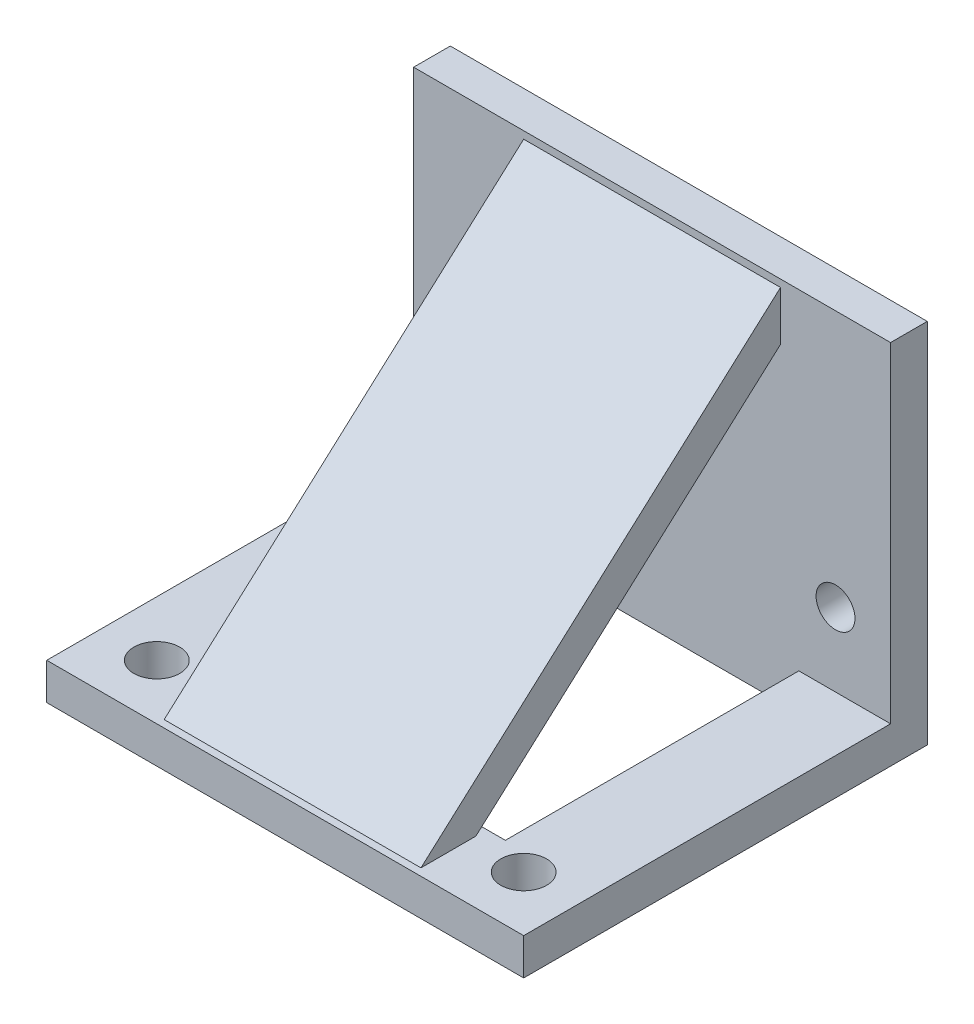
SolidWorks part; units mm, degrees
other "Markup1"
sketch "Sketch16" [suppressed] plane through (60, 62, 45) normal (0.9182, 0.3955, 0.0203) x (-0.0959, 0.2718, -0.9576)
ref_plane "Front" through (0, 0, 0) normal (0, 0, 1) x (1, 0, 0)
ref_plane "Top" through (0, 0, 0) normal (0, 1, 0) x (1, 0, 0)
ref_plane "Right" through (0, 0, 0) normal (1, 0, 0) x (0, 0, -1)
sketch "Sketch1" plane through (0, 0, 0) normal (0, 0, 1) x (1, 0, 0)
  line L1 (-32.5, 0) -> (32.5, 0)
  line L2 (-32.5, 0) -> (-32.5, 50)
  line L3 (-32.5, 50) -> (32.5, 50)
  line L4 (32.5, 0) -> (32.5, 50)
  line L7 (0, 11.4259) -> (0, -9.2664) construction
  point P4 (0, 0)
  dimension "D1" = 50
  dimension "D2" = 65
extrude "Boss-Extrude1" add sketch "Sketch1" along normal blind 5 contours L1 L4 L3 L2 region at (0, 25, 0)
sketch "Sketch2" plane through (0, 0, 0) normal (0, 1, 0) x (1, 0, 0)
  line L0 (0, 7.4706) -> (0, -16.6901) construction
  line L1 (-25, 85) -> (-25, 5) construction
  line L2 (-32.5, 0) -> (-17.5, 0)
  line L3 (-32.5, 0) -> (-32.5, 91)
  line L4 (-32.5, 91) -> (-17.5, 91)
  line L5 (-17.5, 0) -> (-17.5, 91)
  line L8 (17.5, 0) -> (17.5, 91)
  line L9 (32.5, 91) -> (17.5, 91)
  line L10 (32.5, 0) -> (32.5, 91)
  line L11 (32.5, 0) -> (17.5, 0)
  line L12 (-21.75, 85) -> (-21.75, 5)
  line L15 (-28.25, 85) -> (-28.25, 5)
  line L16 (25, 85) -> (25, 5) construction
  line L17 (21.75, 85) -> (21.75, 5)
  line L18 (28.25, 85) -> (28.25, 5)
  arc A4 (-21.75, 85) -> (-28.25, 85) centre (-25, 85) ccw
  arc A5 (-28.25, 5) -> (-21.75, 5) centre (-25, 5) ccw
  arc A6 (21.75, 85) -> (28.25, 85) centre (25, 85) cw
  arc A7 (28.25, 5) -> (21.75, 5) centre (25, 5) cw
  point P9 (-25, 45)
  point P17 (25, 45)
  dimension "D3" = 3.25
  dimension "D5" = 5
  dimension "D1" = 91
  dimension "D2" = 15
  dimension "D4" = 6
extrude "Boss-Extrude3" [suppressed] add sketch "Sketch2" along normal blind 5
sketch "Sketch7" plane through (0, 0, 5) normal (0, 0, 1) x (1, 0, 0)
  line L1 (-32.5, 50) -> (32.5, 50)
  line L2 (-32.5, 50) -> (-32.5, 0)
  line L3 (-32.5, 0) -> (32.5, 0)
  line L4 (32.5, 50) -> (32.5, 0)
extrude "Boss-Extrude5" add sketch "Sketch7" along normal blind 50
sketch "Sketch8" plane through (-32.5, 0, 0) normal (-1, 0, 0) x (0, 0, 1)
  line L0 (55, 50) -> (5, 50)
  line L1 (55, 50) -> (0, 50) construction
  line L2 (5, 50) -> (5, 49)
  line L3 (5, 49) -> (54, 5)
  line L5 (54, 5) -> (55, 5)
  line L6 (55, 50) -> (55, 0) construction
  line L7 (55, 5) -> (55, 50)
  line L8 (0, 0) -> (0, 50) construction
  dimension "D1" = 5
  dimension "D2" = 1
  dimension "D3" = 1
  dimension "D4" = 5
extrude "Cut-Extrude4" cut sketch "Sketch8" against normal through all
sketch "Sketch9" plane through (0, 0, 5) normal (0, 0, 1) x (1, 0, 0)
  line L0 (19, 56.4751) -> (19, -5.9092) construction
  line L1 (32.5, 50) -> (-32.5, 50) construction
  line L2 (0, 50) -> (0, 0) construction
  line L3 (-19, 58.7509) -> (-19, -17.8238) construction
  line L4 (-32.5, 0) -> (32.5, 0) construction
  circle A0 centre (-25, 15) radius 2.65
  circle A3 centre (25, 15) radius 2.65
  dimension "D1" = 5.3
  dimension "D2" = 25
  dimension "D3" = 15
  dimension "D4" = 19
  dimension "D5" = 19
extrude "Cut-Extrude5" cut sketch "Sketch9" against normal through all
sketch "Sketch10" plane through (0, 5, 0) normal (0, 1, 0) x (1, 0, 0)
  line L0 (0, 0) -> (0, -55) construction
  line L1 (32.5, -55) -> (-32.5, -55) construction
  circle A0 centre (-25, -47.5) radius 3.125
  circle A2 centre (25, -47.5) radius 3.125
  dimension "D1" = 6.25
  dimension "D2" = 7.5
  dimension "D3" = 25
extrude "Cut-Extrude6" cut sketch "Sketch10" against normal through all
sketch "Sketch11" [suppressed] plane through (0, 0, 10) normal (0, 0, 1) x (1, 0, 0)
  line L0 (-32.5, 0) -> (32.5, 0) construction
  line L1 (-32.5, 50) -> (-17.5, 50)
  line L2 (-32.5, 50) -> (-32.5, 0)
  line L3 (-32.5, 0) -> (-17.5, 0)
  line L4 (-17.5, 50) -> (-17.5, 0)
  line L6 (0, 50) -> (0, 0) construction
  line L7 (-32.5, 50) -> (32.5, 50) construction
  line L8 (17.5, 50) -> (17.5, 0)
  line L9 (32.5, 0) -> (17.5, 0)
  line L10 (32.5, 50) -> (32.5, 0)
  line L11 (32.5, 50) -> (17.5, 50)
  dimension "D1" = 15
extrude "Boss-Extrude6" [suppressed] add sketch "Sketch11" along normal blind 35
sketch "Sketch12" [suppressed] plane through (-32.5, 0, 0) normal (-1, 0, 0) x (0, 0, 1)
  line L0 (10, 50) -> (10, 35)
  line L1 (45, 50) -> (0, 50) construction
  line L2 (10, 35) -> (35, 5)
  line L3 (35, 5) -> (45, 5)
  line L4 (45, 50) -> (45, 0) construction
  line L5 (45, 5) -> (45, 50)
  line L6 (45, 50) -> (10, 50)
  line L7 (45, 0) -> (-122, 0) construction
  line L8 (0, 5) -> (0, 50) construction
  dimension "D1" = 15
  dimension "D2" = 5
  dimension "D3" = 10
  dimension "D4" = 10
extrude "Cut-Extrude7" [suppressed] cut sketch "Sketch12" against normal through all
sketch "Sketch20" [suppressed] plane through (0, 0, 10) normal (0, 0, 1) x (1, 0, 0)
  line L0 (32.5, 50) -> (32.5, 0) construction
  line L5 (-32.5, 50) -> (32.5, 50)
  line L6 (-32.5, 50) -> (-32.5, 55)
  line L7 (-32.5, 55) -> (32.5, 55)
  line L8 (32.5, 50) -> (32.5, 55)
  dimension "D1" = 5
extrude "Boss-Extrude7" [suppressed] add sketch "Sketch20" against normal up to surface (10 mm away)
sketch "Sketch13" [suppressed] plane through (0, 0, 5) normal (0, 0, 1) x (1, 0, 0)
  line L0 (0, 62) -> (0, 0) construction
  line L1 (32.5, 55) -> (-32.5, 55) construction
  circle A0 centre (-25, 20) radius 3.125
  circle A1 centre (25, 20) radius 3.125
  dimension "D1" = 6.25
  dimension "D2" = 35
  dimension "D3" = 25
extrude "Cut-Extrude8" [suppressed] cut sketch "Sketch13" against normal blind 15
sketch "Sketch14" [suppressed] plane through (0, 5, 0) normal (0, 1, 0) x (1, 0, 0)
  line L1 (-17.5, -45) -> (-32.5, -45) construction
  line L2 (-17.5, -45) -> (-32.5, -45)
  line L3 (-32.5, -35) -> (-32.5, -45) construction
  line L4 (-32.5, -35) -> (-32.5, -45)
  line L5 (0, 0) -> (0, -45) construction
  circle A0 centre (-25, -40) radius 3.125
  circle A1 centre (25, -40) radius 3.125
  point P2 (-25, -45)
  point P6 (-32.5, -40)
  dimension "D1" = 6.25
extrude "Cut-Extrude9" [suppressed] cut sketch "Sketch14" against normal blind 15 contours A0 | A1
sketch "Sketch21" [suppressed] plane through (0, 0, 0) normal (0, 1, 0) x (1, 0, 0)
  line L0 (0, 10.9853) -> (0, -16.7679) construction
  line L1 (32.5, -5) -> (-32.5, -5) construction
  line L2 (32.5, 3) -> (47.5, 3)
  line L3 (32.5, 3) -> (32.5, -5)
  line L4 (32.5, -5) -> (47.5, -5)
  line L5 (47.5, 3) -> (47.5, -5)
  line L6 (34.1921, -1) -> (44.0025, -1) construction
  line L7 (32.5, 3) -> (47.5, 3)
  line L8 (32.5, -5) -> (47.5, -5)
  line L9 (32.5, 3) -> (47.5, 3)
  line L10 (32.5, -5) -> (47.5, -5)
  line L11 (32.5, 3) -> (47.5, 3)
  line L12 (32.5, -5) -> (47.5, -5)
  line L13 (32.5, 3) -> (47.5, 3)
  line L14 (32.5, -5) -> (47.5, -5)
  line L15 (32.5, 3) -> (47.5, 3)
  line L16 (32.5, -5) -> (47.5, -5)
  line L17 (32.5, 3) -> (47.5, 3)
  line L18 (32.5, -5) -> (47.5, -5)
  line L19 (32.5, 3) -> (47.5, 3)
  line L20 (32.5, -5) -> (47.5, -5)
  line L21 (32.5, 3) -> (47.5, 3)
  line L22 (32.5, -5) -> (47.5, -5)
  line L23 (32.5, 3) -> (47.5, 3)
  line L24 (32.5, -5) -> (47.5, -5)
  line L29 (32.5, 0) -> (32.5, 91) construction
  line L30 (32.5, 3) -> (47.5, 3)
  line L31 (32.5, -5) -> (47.5, -5)
  line L32 (32.5, 3) -> (47.5, 3)
  line L33 (32.5, -5) -> (47.5, -5)
  line L34 (32.5, 3) -> (47.5, 3)
  line L35 (32.5, -5) -> (47.5, -5)
  line L36 (32.5, 3) -> (47.5, 3)
  line L37 (32.5, -5) -> (47.5, -5)
  line L38 (32.5, 3) -> (47.5, 3)
  line L39 (32.5, -5) -> (47.5, -5)
  line L40 (32.5, 3) -> (47.5, 3)
  line L41 (32.5, -5) -> (47.5, -5)
  line L42 (32.5, 3) -> (47.5, 3)
  line L43 (32.5, -5) -> (47.5, -5)
  line L44 (32.5, 3) -> (47.5, 3)
  line L45 (32.5, -5) -> (47.5, -5)
  line L46 (32.5, 3) -> (47.5, 3)
  line L47 (32.5, -5) -> (47.5, -5)
  line L48 (32.5, 3) -> (47.5, 3)
  line L49 (32.5, -5) -> (47.5, -5)
  line L50 (-47.5, 3) -> (-32.5, 3)
  line L51 (-47.5, 3) -> (-47.5, -5)
  line L52 (-47.5, -5) -> (-32.5, -5)
  line L53 (-32.5, 3) -> (-32.5, -5)
  line L54 (-47.5, -1) -> (-32.5, -1) construction
  line L55 (-47.5, 3) -> (-32.5, 3)
  line L56 (-47.5, -5) -> (-32.5, -5)
  line L57 (-47.5, 3) -> (-32.5, 3)
  line L58 (-47.5, -5) -> (-32.5, -5)
  line L59 (-47.5, 3) -> (-32.5, 3)
  line L60 (-47.5, -5) -> (-32.5, -5)
  line L61 (-47.5, 3) -> (-32.5, 3)
  line L62 (-47.5, -5) -> (-32.5, -5)
  line L63 (-47.5, 3) -> (-32.5, 3)
  line L64 (-47.5, -5) -> (-32.5, -5)
  line L65 (-47.5, 3) -> (-32.5, 3)
  line L66 (-47.5, -5) -> (-32.5, -5)
  line L67 (-47.5, 3) -> (-32.5, 3)
  line L68 (-47.5, -5) -> (-32.5, -5)
  line L69 (-47.5, 3) -> (-32.5, 3)
  line L70 (-47.5, -5) -> (-32.5, -5)
  line L71 (-47.5, 3) -> (-32.5, 3)
  line L72 (-47.5, -5) -> (-32.5, -5)
  line L73 (-47.5, 3) -> (-32.5, 3)
  line L74 (-47.5, -5) -> (-32.5, -5)
  line L75 (-47.5, 3) -> (-32.5, 3)
  line L76 (-47.5, -5) -> (-32.5, -5)
  line L77 (-47.5, 3) -> (-32.5, 3)
  line L78 (-47.5, -5) -> (-32.5, -5)
  line L79 (-47.5, 3) -> (-32.5, 3)
  line L80 (-47.5, -5) -> (-32.5, -5)
  line L81 (-47.5, 3) -> (-32.5, 3)
  line L82 (-47.5, -5) -> (-32.5, -5)
  line L83 (-47.5, 3) -> (-32.5, 3)
  line L84 (-47.5, -5) -> (-32.5, -5)
  line L85 (-47.5, 3) -> (-32.5, 3)
  line L86 (-47.5, -5) -> (-32.5, -5)
  line L87 (-47.5, 3) -> (-32.5, 3)
  line L88 (-47.5, -5) -> (-32.5, -5)
  line L89 (-47.5, 3) -> (-32.5, 3)
  line L90 (-47.5, -5) -> (-32.5, -5)
  line L91 (-47.5, 3) -> (-32.5, 3)
  line L92 (-47.5, -5) -> (-32.5, -5)
  line L93 (-32.5, 91) -> (-32.5, 0) construction
  circle A0 centre (40, -1) radius 2.75
  circle A2 centre (-40, -1) radius 2.75
  point P31 (-40, -1)
  dimension "D1" = 5.5
  dimension "D5" = 5.5
  dimension "D2" = 15
  dimension "D3" = 40
  dimension "D4" = 8
  dimension "D6" = 15
  dimension "D7" = 8
extrude "Boss-Extrude8" [suppressed] add sketch "Sketch21" along normal blind 10 contours L5 L2 L3 L4 A0 | L53 L50 L51 L52 A2
sketch "Sketch23" [suppressed] plane through (0, 0, 0) normal (0, 0, 1) x (1, 0, 0)
  circle A0 centre (0, 25) radius 12.5
  dimension "D1" = 25
  dimension "D2" = 25
extrude "Cut-Extrude13" [suppressed] cut sketch "Sketch23" against normal through all both and the other way through all
sketch "Sketch24" plane through (32.5, 0, 0) normal (1, 0, 0) x (0, 0, -1)
  line L0 (-5, 49) -> (-54, 5) construction
  line L1 (-5, 49) -> (-54, 5)
  line L2 (-54, 5) -> (-5, 5)
  line L3 (-5, 5) -> (-5, 49)
extrude "Cut-Extrude14" cut sketch "Sketch24" against normal blind 15
extrude "Cut-Extrude15" cut sketch "Sketch24<2>" along normal blind 15 from surface starting at face at (-32.5, 22.7143, 24.8571)
sketch "Sketch24<2>" plane through (32.5, 0, 0) normal (1, 0, 0) x (0, 0, -1) same geometry as "Sketch24"
sketch "Sketch25" plane through (32.5, 0, 0) normal (1, 0, 0) x (0, 0, -1)
  line L0 (-5, 42.28) -> (-46.5164, 5)
  line L3 (-5, 49) -> (-54, 5)
  line L4 (-54, 5) -> (-5, 5)
  line L5 (-5, 5) -> (-5, 49)
  line L6 (-5, 49) -> (-54, 5)
  line L7 (-54, 5) -> (-5, 5)
  line L8 (-5, 5) -> (-5, 49)
  line M5 (-5, 50) -> (-5, 5)
  line M6 (-5, 5) -> (-55, 5)
  dimension "D2" = 5
  dimension "D1" = 0
extrude "Cut-Extrude16" cut sketch "Sketch25" against normal through all contours L0 M5 M6 region at (32.5, 17.4267, 18.8388)
sketch "Sketch26" plane through (0, 0, 0) normal (0, -1, 0) x (1, 0, 0)
  line L1 (-20, 45) -> (20, 45)
  line L2 (-20, 45) -> (-20, 5)
  line L3 (-20, 5) -> (20, 5)
  line L4 (20, 45) -> (20, 5)
  line L5 (-20, 45) -> (20, 5) construction
  line L6 (-20, 5) -> (20, 45) construction
  point P0 (0, 25)
  dimension "D1" = 40
  dimension "D2" = 40
  dimension "D3" = 5
extrude "Cut-Extrude17" cut sketch "Sketch26" against normal up to next
